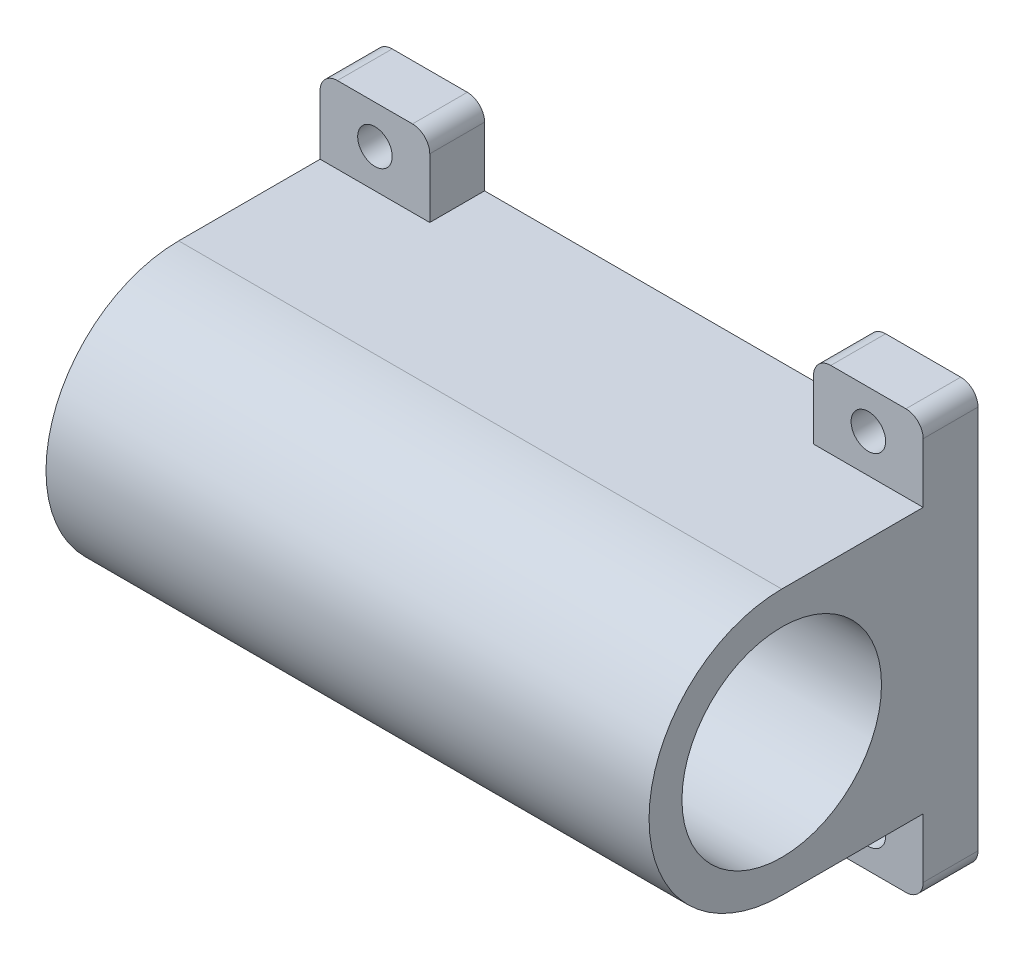
SolidWorks part; units mm, degrees
material "Custom Plastic"
ref_plane "X-Y Datum" through (0, 0, 0) normal (0, 0, 1) x (1, 0, 0)
ref_plane "X-Z Datum" through (0, 0, 0) normal (0, 1, 0) x (1, 0, 0)
ref_plane "Y-Z Datum" through (0, 0, 0) normal (1, 0, 0) x (0, 0, -1)
sketch "Sketch1" plane through (0, 0, 0) normal (0, 0, 1) x (1, 0, 0)
  line L1 (-34.925, -15.367) -> (34.925, -15.367)
  line L2 (-34.925, -15.367) -> (-34.925, 15.367)
  line L3 (-34.925, 15.367) -> (34.925, 15.367)
  line L4 (34.925, -15.367) -> (34.925, 15.367)
  line L5 (-34.925, -15.367) -> (34.925, 15.367) construction
  line L6 (-34.925, 15.367) -> (34.925, -15.367) construction
  point P0 (0, 0)
  dimension "D1" = 69.85
  dimension "D2" = 30.734
extrude "Boss-Extrude1" add sketch "Sketch1" along normal blind 38.1
sketch "Sketch2" plane through (34.925, 0, 0) normal (1, 0, 0) x (0, 0, -1)
  line L0 (-38.1, 0) -> (-38.1, -15.367)
  line L2 (-38.1, -15.367) -> (-38.1, 15.367) construction
  line L3 (-38.1, -15.367) -> (0, -15.367)
  line L4 (0, -15.367) -> (0, 0.3889)
  line L5 (0, -15.367) -> (0, 15.367) construction
  circle A0 centre (-22.733, 0) radius 11.557
  circle A1 centre (-22.733, 0) radius 15.367
  line M2 (0, 15.367) -> (-38.1, 15.367)
  line M3 (-38.1, 15.367) -> (-38.1, -15.367)
  line M4 (-38.1, -15.367) -> (0, -15.367)
  dimension "D1" = 23.114
  dimension "D2" = 30.734
extrude "Cut-Extrude1" cut sketch "Sketch2" against normal through all contours A1 M2 M3 | A1 M3 M4 | A0 region at (34.925, -11.9345, 34.6675) region at (34.925, 11.9345, 34.6675) region at (34.925, 0, 22.733)
sketch "Sketch5" plane through (0, 0, 0) normal (0, 0, -1) x (-1, 0, 0)
  line L0 (-28.575, 24.257) -> (-28.575, 15.367) construction
  line L1 (-34.925, 15.367) -> (-22.225, 15.367)
  line L2 (-34.925, 15.367) -> (-34.925, 24.257)
  line L3 (-34.925, 24.257) -> (-22.225, 24.257)
  line L4 (-22.225, 15.367) -> (-22.225, 24.257)
  circle A0 centre (-28.575, 19.812) radius 2
  dimension "D1" = 8.89
  dimension "D2" = 12.7
extrude "Boss-Extrude2" add sketch "Sketch5" against normal blind 6.35
mirror "Mirror1" about plane through (0, 0, 0) normal (0, 1, 0) of "Boss-Extrude2"
mirror "Mirror2" about plane through (0, 0, 0) normal (1, 0, 0) of "Mirror1"
fillet "Fillet1" radius 2 8 edges at (34.925, -24.257, 3.175) (22.225, -24.257, 3.175) (-22.225, -24.257, 3.175) (-34.925, -24.257, 3.175) (-34.925, 24.257, 3.175) (-22.225, 24.257, 3.175) (34.925, 24.257, 3.175) (22.225, 24.257, 3.175)
